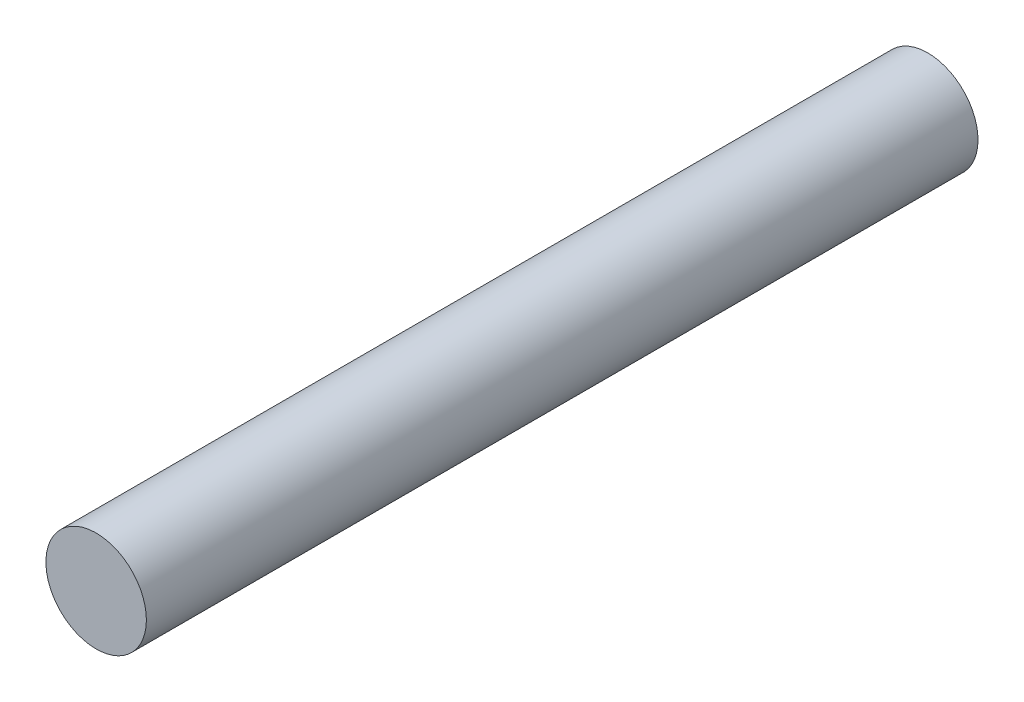
SolidWorks part; units mm, degrees
ref_plane "Front Plane" through (0, 0, 0) normal (0, 0, 1) x (1, 0, 0)
ref_plane "Top Plane" through (0, 0, 0) normal (0, 1, 0) x (1, 0, 0)
ref_plane "Right Plane" through (0, 0, 0) normal (1, 0, 0) x (0, 0, -1)
sketch "Sketch2" plane through (0, 0, 0) normal (0, 0, 1) x (1, 0, 0)
  circle A0 centre (0, 0) radius 7.25
  dimension "D1" = 14.5
extrude "Boss-Extrude1" add sketch "Sketch2" along normal blind 120
